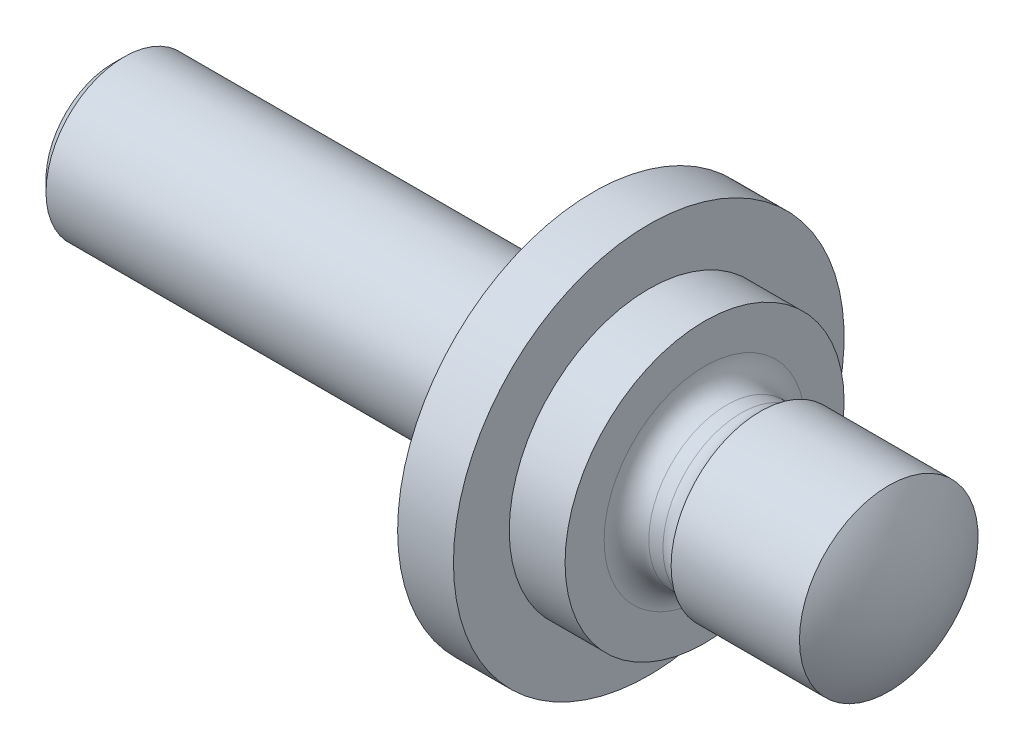
SolidWorks part; units mm, degrees
ref_plane "Ön Düzlem" through (0, 0, 0) normal (0, 0, 1) x (1, 0, 0)
ref_plane "Üst Düzlem" through (0, 0, 0) normal (0, 1, 0) x (1, 0, 0)
ref_plane "Sağ Düzlem" through (0, 0, 0) normal (1, 0, 0) x (0, 0, -1)
sketch "Çizim1" plane through (0, 0, 0) normal (0, 0, 1) x (1, 0, 0)
  line L0 (0, 0) -> (51.6714, 0) construction
  line L1 (0, 0) -> (0, 7)
  line L2 (0, 7) -> (43, 7)
  line L3 (48, 12.5) -> (48, 17.5)
  line L4 (48, 17.5) -> (43, 17.5)
  line L5 (43, 17.5) -> (43, 7)
  line L6 (48, 12.5) -> (53, 12.5)
  line L7 (53, 12.5) -> (53, 7)
  line L8 (53, 7) -> (58, 7)
  line L9 (58, 7) -> (58, 8)
  line L10 (58, 8) -> (72, 8)
  line L11 (72, 8) -> (72, 0)
  line L12 (0, 0) -> (72, 0)
  dimension "D1" = 48
  dimension "D2" = 7
  dimension "D3" = 35
  dimension "D4" = 5
  dimension "D5" = 5
  dimension "D6" = 25
  dimension "D7" = 24
  dimension "D8" = 16
  dimension "D9" = 5
revolve "Döndür1" add sketch "Çizim1" angle 360 about L0
fillet "Radyus2" radius 2 2 edges at (58, 0, 7) (53, 0, 7)
chamfer "Pah1" distance 1 angle 45 1 edges at (0, 0, 7)
cosmetic thread "Kozmetik Diş Açma2" parameters "D2"=11.797
sketch "Çizim2" plane through (0, 0, 0) normal (0, 0, 1) x (1, 0, 0)
  line L0 (72, 8) -> (58, 8) construction
  line L2 (72, 0) -> (67.2528, 0) construction
  line L3 (72, -8) -> (72, 8) construction
  line L4 (69.5, 8) -> (72, 8)
  line L5 (72, 8) -> (72, 0)
  line L6 (72, 8) -> (72.4878, 8)
  line L7 (72.4878, 8) -> (72.4878, 0)
  line L8 (72.4878, 0) -> (72, 0)
  arc A0 (69.5, 8) -> (72, 0) centre (57.95, 0) cw
  dimension "D1" = 2.5
revolve "Kes-Döndür1" cut sketch "Çizim2" angle 360 about L2 region at (71.263, 6.0373, 0) region at (72.2439, 4, 0)
